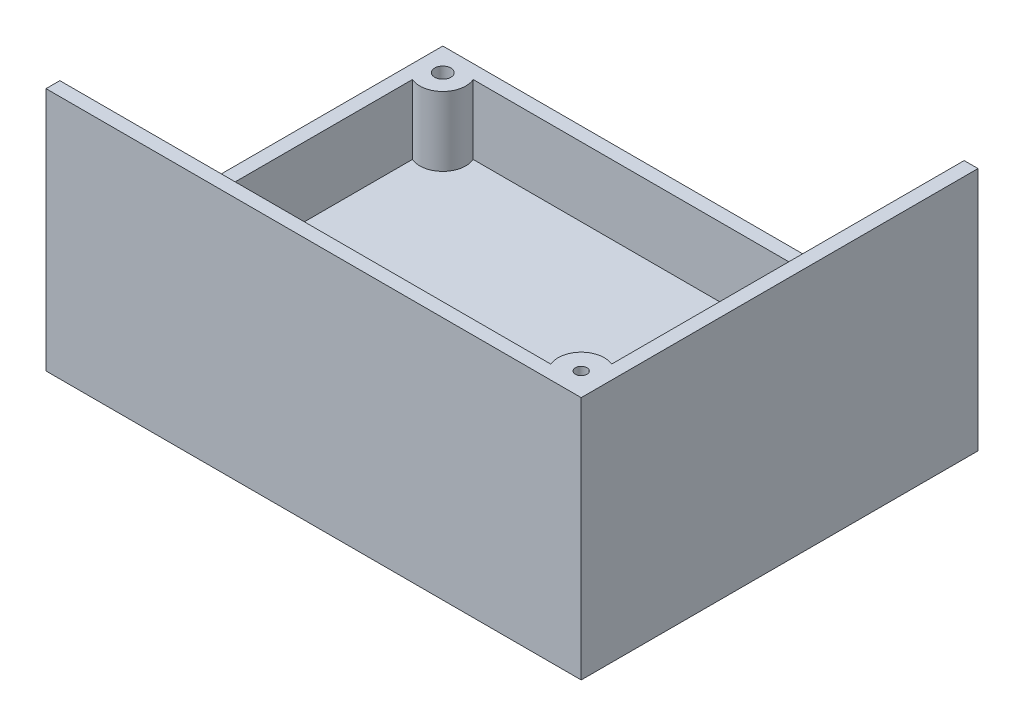
SolidWorks part; units mm, degrees
ref_plane "前视基准面" through (0, 0, 0) normal (0, 0, 1) x (1, 0, 0)
ref_plane "上视基准面" through (0, 0, 0) normal (0, 1, 0) x (1, 0, 0)
ref_plane "右视基准面" through (0, 0, 0) normal (1, 0, 0) x (0, 0, -1)
other "Configuration Table"
sketch "Sketch1" plane through (0, 0, 0) normal (0, 1, 0) x (1, 0, 0)
  line L0 (-3, -3) -> (113, -3)
  line L1 (0, 0) -> (110, 0)
  line L2 (0, 0) -> (0, 80)
  line L3 (0, 80) -> (110, 80)
  line L4 (110, 0) -> (110, 80)
  line L5 (113, -3) -> (113, 83)
  line L6 (-3, 83) -> (113, 83)
  line L7 (-3, -3) -> (-3, 83)
  dimension "D1" = 80
  dimension "D2" = 110
  dimension "D3" = 3
extrude "Boss-Extrude1" add sketch "Sketch1" along normal blind 3 contours L2 L1 L4 L3
extrude "Boss-Extrude2" add sketch "Sketch1<3>" along normal blind 53
sketch "Sketch1<3>" plane through (0, 0, 0) normal (0, 1, 0) x (1, 0, 0) same geometry as "Sketch1"
sketch "Sketch2" plane through (-3, 0, 0) normal (-1, 0, 0) x (0, 0, 1)
  line L0 (-83, 0) -> (3, 0) construction
  circle A0 centre (-7, 18) radius 4.5
  dimension "D2" = 9
  dimension "D3" = 18
  dimension "D1" = 7
extrude "Cut-Extrude1" cut sketch "Sketch2" against normal blind 53
sketch "Sketch3" plane through (0, 0, -83) normal (0, 0, -1) x (-1, 0, 0)
  line L0 (-113, 53) -> (-113, 0) construction
  line L1 (-113, 0) -> (3, 0) construction
  circle A0 centre (-93, 18) radius 5.5
  dimension "D3" = 11
  dimension "D1" = 20
  dimension "D2" = 18
extrude "Cut-Extrude2" cut sketch "Sketch3" against normal blind 53
sketch "Sketch5" plane through (0, 0, -83) normal (0, 0, -1) x (-1, 0, 0)
  line L1 (-110, 53) -> (3, 53)
  line L2 (-110, 53) -> (-110, 18)
  line L3 (-110, 18) -> (3, 18)
  line L4 (3, 53) -> (3, 18)
  line L5 (3, 53) -> (3, 0) construction
  circle A0 centre (-93, 18) radius 5.5 construction
  dimension "D1" = 0
  dimension "D2" = 0
extrude "Cut-Extrude3" cut sketch "Sketch5" against normal blind 83
sketch "Sketch6" plane through (0, 3, 0) normal (0, 1, 0) x (1, 0, 0)
  line L0 (87.5, 83) -> (-3, 83) construction
  line L1 (-3, 11.5) -> (-3, 83) construction
  circle A0 centre (2, 78) radius 5
  dimension "D1" = 10
extrude "Boss-Extrude3" add sketch "Sketch6" along normal blind 15
sketch "Sketch8" plane through (0, 18, 0) normal (0, 1, 0) x (1, 0, 0)
  circle A0 centre (2, 78) radius 1.75
  dimension "D1" = 3.5
extrude "Cut-Extrude4" cut sketch "Sketch8" against normal blind 25
sketch "Sketch9" plane through (0, 0, 0) normal (0, -1, 0) x (-1, 0, 0)
  circle A0 centre (-2, 78) radius 3
  dimension "D1" = 6
extrude "Cut-Extrude5" cut sketch "Sketch9" against normal blind 10
sketch "Sketch10" plane through (0, 3, 0) normal (0, 1, 0) x (1, 0, 0)
  line L0 (113, -3) -> (113, 83) construction
  line L1 (-3, -3) -> (113, -3) construction
  circle A0 centre (108, 2) radius 5
  circle A1 centre (108, 2) radius 1.25
  dimension "D1" = 10
  dimension "D2" = 2.5
extrude "Boss-Extrude4" add sketch "Sketch10" along normal blind 50
sketch "Sketch11" plane through (0, 3, 0) normal (0, 1, 0) x (1, 0, 0)
  line L0 (110, 6.5826) -> (110, 80) construction
  line L1 (110, 0) -> (76.5353, 0)
  line L2 (110, 0) -> (110, 24.9685)
  line L3 (110, 24.9685) -> (76.5353, 24.9685)
  line L4 (76.5353, 0) -> (76.5353, 24.9685)
  line L5 (0, 0) -> (103.4174, 0) construction
extrude "Cut-Extrude7" cut sketch "Sketch11" along normal blind 35
